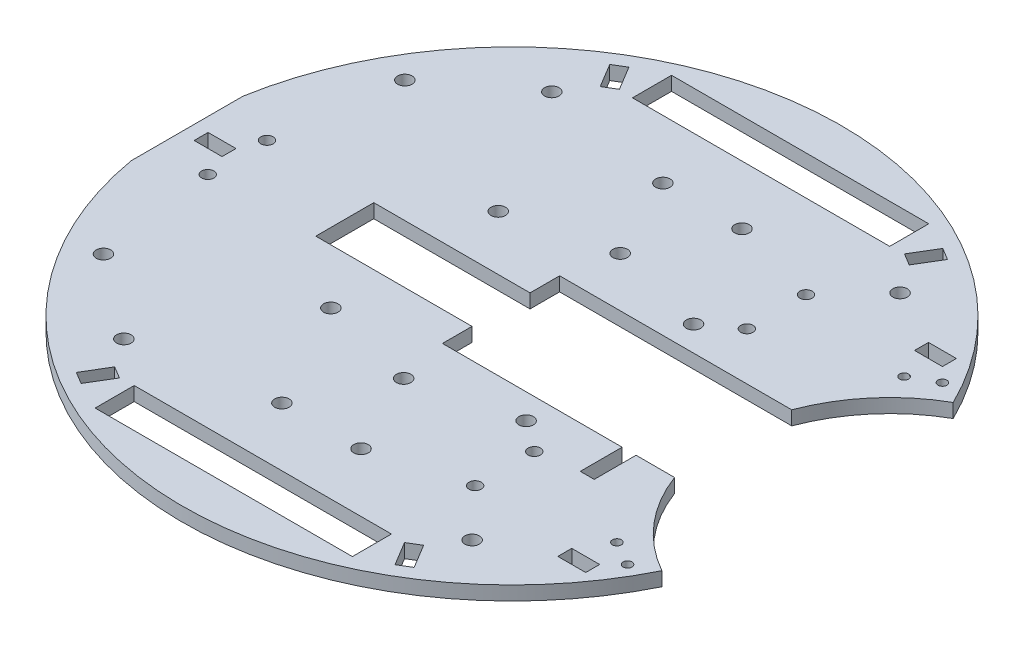
SolidWorks part; units mm, degrees
material "Acrylic (Medium-high impact)"
ref_plane "Front Plane" through (0, 0, 0) normal (0, 0, 1) x (1, 0, 0)
ref_plane "Top Plane" through (0, 0, 0) normal (0, 1, 0) x (1, 0, 0)
ref_plane "Right Plane" through (0, 0, 0) normal (1, 0, 0) x (0, 0, -1)
sketch "Sketch1" plane through (0, 0, 0) normal (0, 1, 0) x (1, 0, 0)
  line L0 (67.2709, 33.1606) -> (86.0323, 0) construction
  line L1 (86.0323, 0) -> (67.2709, -33.1606) construction
  line L2 (0, 65.5895) -> (0, 75) construction
  line L3 (-29.2721, -56.6995) -> (29.2721, -56.6995)
  line L4 (-29.2721, -56.6995) -> (-29.2721, -65.5895)
  line L5 (-29.2721, -65.5895) -> (29.2721, -65.5895)
  line L6 (29.2721, -56.6995) -> (29.2721, -65.5895)
  line L7 (-29.2721, 65.5895) -> (29.2721, 65.5895)
  line L8 (-29.2721, 65.5895) -> (-29.2721, 56.6995)
  line L9 (-29.2721, 56.6995) -> (29.2721, 56.6995)
  line L10 (29.2721, 65.5895) -> (29.2721, 56.6995)
  line L11 (29.2721, 65.5895) -> (30.566, 68.4888) construction
  line L12 (29.2721, -65.5895) -> (30.566, -68.4888) construction
  line L13 (-62.4869, 6.731) -> (-62.4869, -6.731) construction
  line L14 (-62.4869, 0) -> (-73.9169, 0) construction
  line L16 (58.9661, -42.1806) -> (52.6161, -42.1806)
  line L17 (58.9661, -42.1806) -> (58.9661, -39.0056)
  line L18 (58.9661, -39.0056) -> (52.6161, -39.0056)
  line L19 (52.6161, -42.1806) -> (52.6161, -39.0056)
  line L20 (58.9661, 42.1806) -> (52.6161, 42.1806)
  line L21 (58.9661, 42.1806) -> (58.9661, 39.0056)
  line L22 (60.7114, 44.0354) -> (67.2709, 33.1606) construction
  line L23 (0, 0) -> (86.0323, 0) construction
  line L24 (52.6161, 42.1806) -> (52.6161, 39.0056)
  line L25 (58.9661, 39.0056) -> (52.6161, 39.0056)
  line L28 (-39.6269, -48.6985) -> (0, -24.638) construction
  line L29 (0, -24.638) -> (39.6269, -48.6985) construction
  line L30 (-39.6269, -48.6985) -> (39.6269, -48.6985) construction
  line L31 (0, -24.638) -> (0, -48.6985) construction
  line L32 (-2.4867, 6.604) -> (-2.4867, 13.335) construction
  line L33 (38.4073, -13.335) -> (-2.4867, -13.335) construction
  line L34 (-2.4867, -13.335) -> (-2.4867, -6.604) construction
  line L35 (-2.4867, 13.335) -> (38.4073, 13.335) construction
  line L36 (38.4073, 13.335) -> (41.5823, 13.335)
  line L37 (32.441, -56.8953) -> (35.7191, -62.3337)
  line L38 (32.441, -56.8953) -> (35.1602, -55.2563)
  line L39 (35.7191, -62.3337) -> (38.4383, -60.6947)
  line L40 (35.1602, -55.2563) -> (38.4383, -60.6947)
  line L41 (-58.6769, -34.29) -> (-58.6769, 34.29) construction
  line L42 (0, 0) -> (-16.51, 0) construction
  line L43 (-58.6769, 0) -> (-62.4869, 0) construction
  line L44 (41.5823, 13.335) -> (50.3421, 13.335)
  line L45 (41.5823, -13.335) -> (46.2813, -13.335)
  line L46 (-2.4867, -6.604) -> (-2.4867, -13.335)
  line L47 (-73.9169, 12.7) -> (-73.9169, -12.7)
  line L48 (38.4073, 13.335) -> (-2.4867, 13.335)
  line L49 (-2.4867, 13.335) -> (-2.4867, 6.604)
  line L50 (-2.4867, -13.335) -> (38.4073, -13.335)
  line L51 (46.2813, -13.335) -> (50.3421, -13.335)
  line L52 (-2.4867, 0) -> (-38.0467, 0) construction
  line L53 (-2.4867, 6.604) -> (-38.0467, 6.604)
  line L54 (14.856, 13.335) -> (14.856, 0) construction
  line L55 (-2.4867, -6.604) -> (-38.0467, -6.604)
  line L56 (-38.0467, 6.604) -> (-38.0467, -6.604)
  line L57 (14.856, 0) -> (14.856, -13.335) construction
  line L58 (32.441, -56.8953) -> (38.4383, -60.6947) construction
  line L59 (35.7191, -62.3337) -> (35.1602, -55.2563) construction
  line L60 (41.5823, -13.335) -> (41.5823, -22.86)
  line L61 (41.5823, -22.86) -> (38.4073, -22.86)
  line L62 (38.4073, -13.335) -> (38.4073, -22.86)
  line L63 (33.8006, -56.0758) -> (0, 0) construction
  line L64 (37.0787, -61.5142) -> (38.7178, -64.2334) construction
  line L65 (-32.441, -56.8953) -> (-35.1602, -55.2563)
  line L66 (-32.441, -56.8953) -> (-35.7191, -62.3337)
  line L67 (-35.7191, -62.3337) -> (-38.4383, -60.6947)
  line L68 (-35.1602, -55.2563) -> (-38.4383, -60.6947)
  line L69 (-35.1602, 55.2563) -> (-38.4383, 60.6947)
  line L70 (-32.441, 56.8953) -> (-35.1602, 55.2563)
  line L71 (-32.441, 56.8953) -> (-35.7191, 62.3337)
  line L72 (-35.7191, 62.3337) -> (-38.4383, 60.6947)
  line L73 (35.1602, 55.2563) -> (38.4383, 60.6947)
  line L74 (32.441, 56.8953) -> (35.1602, 55.2563)
  line L75 (32.441, 56.8953) -> (35.7191, 62.3337)
  line L76 (35.7191, 62.3337) -> (38.4383, 60.6947)
  line L77 (-73.9169, 0) -> (-70.7419, 0) construction
  line L78 (-70.7419, 1.5875) -> (-64.3919, 1.5875)
  line L79 (-70.7419, 1.5875) -> (-70.7419, -1.5875)
  line L80 (-70.7419, -1.5875) -> (-64.3919, -1.5875)
  line L81 (-64.3919, 1.5875) -> (-64.3919, -1.5875)
  arc A0 (67.2709, 33.1606) -> (-73.9169, 12.7) centre (0, 0) ccw
  arc A1 (67.2709, -33.1606) -> (55.0862, -22.225) centre (86.0323, 0) cw
  circle A2 centre (-62.4869, 6.731) radius 1.397
  circle A3 centre (-62.4869, -6.731) radius 1.397
  circle A4 centre (-39.6269, -48.6985) radius 1.651
  circle A5 centre (39.6269, -48.6985) radius 1.651
  circle A6 centre (39.6269, 48.6985) radius 1.651
  circle A7 centre (0, -24.638) radius 1.651
  circle A8 centre (-39.6269, 48.6985) radius 1.651
  circle A9 centre (0, 24.638) radius 1.651
  circle A10 centre (29.2721, -37.6495) radius 1.397
  arc A11 (55.0862, -22.225) -> (50.3421, -13.335) centre (86.0323, 0) cw
  circle A12 centre (-58.6769, 34.29) radius 1.651
  circle A13 centre (62.1411, -35.8306) radius 1.016
  circle A14 centre (56.5708, -32.6791) radius 1.016
  circle A15 centre (-58.6769, -34.29) radius 1.651
  arc A16 (50.3421, 13.335) -> (67.2709, 33.1606) centre (86.0323, 0) cw
  arc A17 (-73.9169, -12.7) -> (67.2709, -33.1606) centre (0, 0) ccw
  circle A18 centre (29.2721, -24.1875) radius 1.397
  circle A19 centre (29.2721, 37.6495) radius 1.397
  circle A20 centre (29.2721, 24.1875) radius 1.397
  circle A21 centre (8.9992, -43.3535) radius 1.651
  circle A22 centre (-9.0008, -43.3535) radius 1.651
  circle A23 centre (-9.0008, 43.3535) radius 1.651
  circle A24 centre (8.9992, 43.3535) radius 1.651
  circle A25 centre (62.1411, 35.8306) radius 1.016
  circle A26 centre (56.5708, 32.6791) radius 1.016
  circle A27 centre (56.5708, 32.6791) radius 1.016 construction
  circle A28 centre (22.2783, 19.05) radius 1.651
  circle A29 centre (22.2783, -19.05) radius 1.651
  circle A30 centre (-22.1717, -19.05) radius 1.651
  circle A31 centre (-22.1717, 19.05) radius 1.651
  circle A32 centre (22.2783, 19.05) radius 1.651 construction
  point P50 (41.5823, 0)
  point P56 (47.9323, 0)
  point P63 (35.4397, -58.795)
  dimension "D1" = 150
  dimension "D7" = 11.43
  dimension "D8" = 2.794
  dimension "D14" = 24.0605
  dimension "D16" = 3.302
  dimension "D22" = 13.208
  dimension "D27" = 3.302
  dimension "D34" = 2.794
  dimension "D2" = 121
  dimension "D3" = 38.1
  dimension "D4" = 58.5441
  dimension "D5" = 8.89
  dimension "D6" = 3.175
  dimension "D9" = 13.462
  dimension "D10" = 6.35
  dimension "D11" = 3.175
  dimension "D12" = 3.175
  dimension "D13" = 3.175
  dimension "D15" = 3.175
  dimension "D18" = 25.4
  dimension "D19" = 26.67
  dimension "D20" = 44.069
  dimension "D21" = 17.3428
  dimension "D23" = 38.1
  dimension "D24" = 9.525
  dimension "D25" = 15.24
  dimension "D26" = 68.58
  dimension "D28" = 44.45
  dimension "D29" = 35.56
  dimension "D30" = 6.35
  dimension "D31" = 88.519
  dimension "D32" = 16.51
  dimension "D33" = 13.462
  dimension "D35" = 19.05
  dimension "D37" = 3.175
  dimension "D38" = 3.175
  dimension "D39" = 3.175
extrude "Boss-Extrude1" add sketch "Sketch1" along normal blind 3.175
equation "\"Diameter\"= 2.75"
equation "\"D4@Sketch1\"=\"Diameter\"*sin(arccos(1-(5/(4*\"Diameter\"))))"
